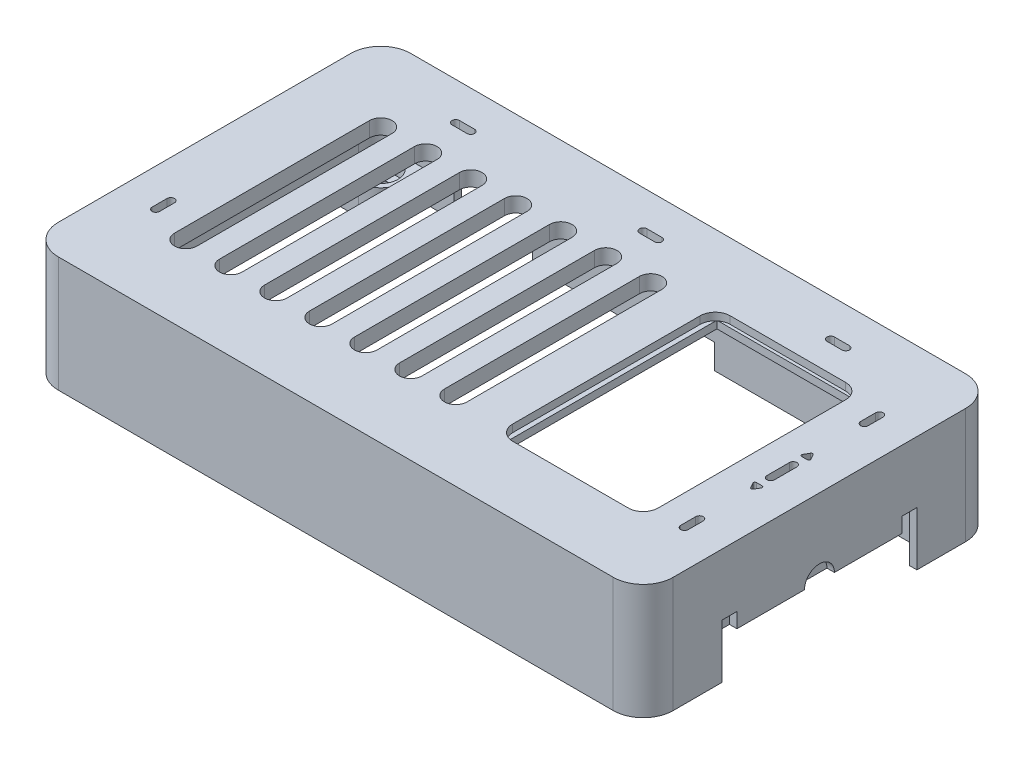
SolidWorks part; units mm, degrees
ref_plane "前视基准面" through (0, 0, 0) normal (0, 0, 1) x (1, 0, 0)
ref_plane "上视基准面" through (0, 0, 0) normal (0, 1, 0) x (1, 0, 0)
ref_plane "右视基准面" through (0, 0, 0) normal (1, 0, 0) x (0, 0, -1)
sketch "草图1" plane through (0, 0, 0) normal (0, 1, 0) x (1, 0, 0)
  line L0 (-1, -3) -> (-1, -42)
  line L1 (3, 0) -> (77, 0) construction
  line L2 (0, -3) -> (0, -42) construction
  line L3 (3, -45) -> (77, -45) construction
  line L4 (80, -3) -> (80, -42) construction
  line L5 (3, -46) -> (77, -46)
  line L6 (81, -3) -> (81, -42)
  line L7 (3, 1) -> (77, 1)
  arc A0 (3, -45) -> (0, -42) centre (3, -42) cw construction
  arc A1 (77, -45) -> (80, -42) centre (77, -42) ccw construction
  arc A2 (80, -3) -> (77, 0) centre (77, -3) ccw construction
  arc A3 (3, 0) -> (0, -3) centre (3, -3) ccw construction
  arc A4 (3, -46) -> (-1, -42) centre (3, -42) cw
  arc A5 (77, -46) -> (81, -42) centre (77, -42) ccw
  arc A6 (81, -3) -> (77, 1) centre (77, -3) ccw
  arc A7 (3, 1) -> (-1, -3) centre (3, -3) ccw
  point P5 (0, 0)
  point P14 (0, 0)
  dimension "D1" = 3
  dimension "D2" = 1
extrude "凸台-拉伸1" add sketch "草图1" against normal blind 2
sketch "草图2" plane through (0, 0, 0) normal (0, 1, 0) x (1, 0, 0)
  line L0 (0, -3) -> (0, -42) construction
  line L1 (3, -45) -> (77, -45) construction
  line L2 (80, -42) -> (80, -3) construction
  line L3 (77, 0) -> (3, 0) construction
  line L4 (-1, -3) -> (-1, -42)
  line L5 (77, 1) -> (3, 1)
  line L6 (81, -42) -> (81, -3)
  line L7 (3, -46) -> (77, -46)
  line L8 (-1, -3) -> (-1, -42) construction
  line L9 (77, 1) -> (3, 1) construction
  line L10 (81, -42) -> (81, -3) construction
  line L11 (3, -46) -> (77, -46) construction
  line L12 (39, -4) -> (41, -4) construction
  line L13 (0, 0) -> (80, 0) construction
  line L14 (0, 0) -> (0, -4) construction
  line L15 (0, -4) -> (80, -4) construction
  line L16 (80, 0) -> (80, -4) construction
  line L17 (39, -3.5) -> (41, -3.5)
  line L18 (39, -4.5) -> (41, -4.5)
  line L19 (0, -4) -> (15, -4) construction
  line L20 (14, -4) -> (16, -4) construction
  line L21 (14, -3.5) -> (16, -3.5)
  line L22 (14, -4.5) -> (16, -4.5)
  line L23 (80, -4) -> (65, -4) construction
  line L24 (64, -4) -> (66, -4) construction
  line L25 (64, -3.5) -> (66, -3.5)
  line L26 (64, -4.5) -> (66, -4.5)
  line L27 (76, -22.5) -> (76, -19.064) construction
  line L28 (80, 0) -> (76, 0) construction
  line L29 (80, 0) -> (80, -45) construction
  line L30 (80, -45) -> (76, -45) construction
  line L31 (76, 0) -> (76, -45) construction
  line L32 (76, -21) -> (76, -24) construction
  line L33 (76.5, -21) -> (76.5, -24)
  line L34 (75.5, -21) -> (75.5, -24)
  line L35 (76, -22.5) -> (76, -25.936) construction
  line L36 (75.8268, -18.514) -> (75.4371, -19.189)
  line L37 (75.6103, -19.489) -> (76.3897, -19.489)
  line L38 (76.5629, -19.189) -> (76.1732, -18.514)
  line L39 (76, -22.5) -> (76, -10.5) construction
  line L40 (76.1732, -26.486) -> (76.5629, -25.811)
  line L41 (76.3897, -25.511) -> (75.6103, -25.511)
  line L42 (75.4371, -25.811) -> (75.8268, -26.486)
  line L43 (76, -9.5) -> (76, -11.5) construction
  line L44 (76.5, -9.5) -> (76.5, -11.5)
  line L45 (75.5, -9.5) -> (75.5, -11.5)
  line L46 (76, -22.5) -> (76, -34.5) construction
  line L47 (76, -33.5) -> (76, -35.5) construction
  line L48 (76.5, -33.5) -> (76.5, -35.5)
  line L49 (75.5, -33.5) -> (75.5, -35.5)
  line L50 (4, 0) -> (4, -33) construction
  line L51 (0, 0) -> (4, 0) construction
  line L52 (0, 0) -> (0, -45) construction
  line L53 (0, -45) -> (4, -45) construction
  line L54 (4, 0) -> (4, -45) construction
  line L55 (4, -32) -> (4, -34) construction
  line L56 (4.5, -32) -> (4.5, -34)
  line L57 (3.5, -32) -> (3.5, -34)
  line L58 (70, -8) -> (54.5978, -8)
  line L59 (80, 0) -> (70, 0) construction
  line L60 (80, 0) -> (80, -10) construction
  line L61 (80, -10) -> (70, -10) construction
  line L62 (70, 0) -> (70, -10) construction
  line L63 (80, -45) -> (70, -45) construction
  line L64 (80, -45) -> (80, -35) construction
  line L65 (80, -35) -> (70, -35) construction
  line L66 (70, -45) -> (70, -35) construction
  line L67 (70, -10) -> (54.5978, -10) construction
  line L68 (70, -10) -> (70, -35) construction
  line L69 (70, -35) -> (54.5978, -35) construction
  line L70 (54.5978, -10) -> (54.5978, -35) construction
  line L71 (52.5978, -10) -> (52.5978, -35)
  line L72 (70, -37) -> (54.5978, -37)
  line L73 (72, -10) -> (72, -35)
  line L74 (72, -37) -> (52.5978, -37) construction
  line L75 (72, -8) -> (72, -37) construction
  line L76 (52.5978, -8) -> (52.5978, -37) construction
  line L77 (72, -8) -> (52.5978, -8) construction
  line L78 (54.5978, -8) -> (70, -8) construction
  line L79 (54.5978, -37) -> (70, -37) construction
  line L80 (8, -8) -> (9.5, -8) construction
  line L85 (0, 0) -> (8, 0) construction
  line L86 (0, 0) -> (0, -8) construction
  line L87 (0, -8) -> (8, -8) construction
  line L88 (8, -0.0281) -> (8, -8.0281) construction
  line L89 (9.5, -9.5) -> (9.5, -35.5) construction
  line L90 (8, -8) -> (9.5, -8) construction
  line L91 (8, -8) -> (8, -9.5) construction
  line L92 (8, -9.5) -> (9.5, -9.5) construction
  line L93 (9.5, -8) -> (9.5, -9.5) construction
  line L94 (8, -37) -> (9.5, -37) construction
  line L95 (8, -37) -> (8, -35.5) construction
  line L96 (8, -35.5) -> (9.5, -35.5) construction
  line L97 (9.5, -37) -> (9.5, -35.5) construction
  line L98 (11, -9.5) -> (11, -35.5)
  line L99 (8, -9.5) -> (8, -35.5)
  line L100 (15.5, -9.5) -> (15.5, -35.5) construction
  line L101 (17, -9.5) -> (17, -35.5)
  line L102 (14, -9.5) -> (14, -35.5)
  line L103 (21.5, -9.5) -> (21.5, -35.5) construction
  line L104 (23, -9.5) -> (23, -35.5)
  line L105 (20, -9.5) -> (20, -35.5)
  line L106 (27.5, -9.5) -> (27.5, -35.5) construction
  line L107 (29, -9.5) -> (29, -35.5)
  line L108 (26, -9.5) -> (26, -35.5)
  line L109 (33.5, -9.5) -> (33.5, -35.5) construction
  line L110 (35, -9.5) -> (35, -35.5)
  line L111 (32, -9.5) -> (32, -35.5)
  line L112 (39.5, -9.5) -> (39.5, -35.5) construction
  line L113 (41, -9.5) -> (41, -35.5)
  line L114 (38, -9.5) -> (38, -35.5)
  line L115 (45.5, -9.5) -> (45.5, -35.5) construction
  line L116 (47, -9.5) -> (47, -35.5)
  line L117 (44, -9.5) -> (44, -35.5)
  arc A0 (0, -42) -> (3, -45) centre (3, -42) ccw construction
  arc A1 (77, -45) -> (80, -42) centre (77, -42) ccw construction
  arc A2 (80, -3) -> (77, 0) centre (77, -3) ccw construction
  arc A3 (3, 0) -> (0, -3) centre (3, -3) ccw construction
  arc A4 (3, 1) -> (-1, -3) centre (3, -3) ccw
  arc A5 (81, -3) -> (77, 1) centre (77, -3) ccw
  arc A6 (77, -46) -> (81, -42) centre (77, -42) ccw
  arc A7 (-1, -42) -> (3, -46) centre (3, -42) ccw
  arc A8 (3, 1) -> (-1, -3) centre (3, -3) ccw construction
  arc A9 (81, -3) -> (77, 1) centre (77, -3) ccw construction
  arc A10 (77, -46) -> (81, -42) centre (77, -42) ccw construction
  arc A11 (-1, -42) -> (3, -46) centre (3, -42) ccw construction
  arc A12 (39, -3.5) -> (39, -4.5) centre (39, -4) ccw
  arc A13 (41, -4.5) -> (41, -3.5) centre (41, -4) ccw
  arc A14 (14, -3.5) -> (14, -4.5) centre (14, -4) ccw
  arc A15 (16, -4.5) -> (16, -3.5) centre (16, -4) ccw
  arc A16 (64, -3.5) -> (64, -4.5) centre (64, -4) ccw
  arc A17 (66, -4.5) -> (66, -3.5) centre (66, -4) ccw
  arc A19 (76.5, -21) -> (75.5, -21) centre (76, -21) ccw
  arc A20 (75.5, -24) -> (76.5, -24) centre (76, -24) ccw
  circle A21 centre (76, -19.064) radius 0.85 construction
  arc A22 (76.5629, -19.189) -> (76.3897, -19.489) centre (76.3897, -19.289) cw
  arc A23 (76.1732, -18.514) -> (75.8268, -18.514) centre (76, -18.614) ccw
  arc A24 (75.4371, -19.189) -> (75.6103, -19.489) centre (75.6103, -19.289) ccw
  circle A25 centre (76, -25.936) radius 0.85 construction
  arc A26 (76.1732, -26.486) -> (75.8268, -26.486) centre (76, -26.386) cw
  arc A27 (76.3897, -25.511) -> (76.5629, -25.811) centre (76.3897, -25.711) cw
  arc A28 (75.6103, -25.511) -> (75.4371, -25.811) centre (75.6103, -25.711) ccw
  arc A29 (76.5, -9.5) -> (75.5, -9.5) centre (76, -9.5) ccw
  arc A30 (75.5, -11.5) -> (76.5, -11.5) centre (76, -11.5) ccw
  arc A31 (76.5, -33.5) -> (75.5, -33.5) centre (76, -33.5) ccw
  arc A32 (75.5, -35.5) -> (76.5, -35.5) centre (76, -35.5) ccw
  arc A33 (4.5, -32) -> (3.5, -32) centre (4, -32) ccw
  arc A34 (3.5, -34) -> (4.5, -34) centre (4, -34) ccw
  arc A35 (70, -37) -> (72, -35) centre (70, -35) ccw
  arc A36 (54.5978, -37) -> (52.5978, -35) centre (54.5978, -35) cw
  arc A37 (72, -10) -> (70, -8) centre (70, -10) ccw
  arc A38 (54.5978, -8) -> (52.5978, -10) centre (54.5978, -10) ccw
  arc A39 (11, -9.5) -> (8, -9.5) centre (9.5, -9.5) ccw
  arc A40 (8, -35.5) -> (11, -35.5) centre (9.5, -35.5) ccw
  arc A41 (17, -9.5) -> (14, -9.5) centre (15.5, -9.5) ccw
  arc A42 (14, -35.5) -> (17, -35.5) centre (15.5, -35.5) ccw
  arc A43 (23, -9.5) -> (20, -9.5) centre (21.5, -9.5) ccw
  arc A44 (20, -35.5) -> (23, -35.5) centre (21.5, -35.5) ccw
  arc A45 (29, -9.5) -> (26, -9.5) centre (27.5, -9.5) ccw
  arc A46 (26, -35.5) -> (29, -35.5) centre (27.5, -35.5) ccw
  arc A47 (35, -9.5) -> (32, -9.5) centre (33.5, -9.5) ccw
  arc A48 (32, -35.5) -> (35, -35.5) centre (33.5, -35.5) ccw
  arc A49 (41, -9.5) -> (38, -9.5) centre (39.5, -9.5) ccw
  arc A50 (38, -35.5) -> (41, -35.5) centre (39.5, -35.5) ccw
  arc A51 (47, -9.5) -> (44, -9.5) centre (45.5, -9.5) ccw
  arc A52 (44, -35.5) -> (47, -35.5) centre (45.5, -35.5) ccw
  point P31 (40, -4)
  point P38 (15, -4)
  point P46 (65, -4)
  point P59 (76, -22.5)
  point P70 (76.7361, -19.489)
  point P86 (75.2639, -25.511)
  point P89 (76, -10.5)
  point P97 (76, -34.5)
  point P109 (4, -33)
  point P154 (9.5, -22.5)
  point P159 (0, 0)
  point P162 (15.5, -22.5)
  point P169 (21.5, -22.5)
  point P176 (27.5, -22.5)
  point P183 (33.5, -22.5)
  point P190 (39.5, -22.5)
  point P197 (45.5, -22.5)
  dimension "D3" = 0.2
  dimension "D4" = 0.2
  dimension "D5" = 2
  dimension "D6" = 2
  dimension "D7" = 7
  dimension "D1" = 0
  dimension "D2" = 1
extrude "切除-拉伸1" cut sketch "草图2" against normal blind 1
sketch "草图3" plane through (0, -2, 0) normal (0, -1, 0) x (1, 0, 0)
  line L0 (76, 11.5) -> (76, 9.5) construction
  line L1 (76, 24) -> (76, 21) construction
  line L2 (14, 3.5) -> (16, 3.5)
  line L3 (16, 4.5) -> (14, 4.5)
  line L4 (14, 3.5) -> (16, 3.5) construction
  line L5 (16, 4.5) -> (14, 4.5) construction
  line L6 (39, 3.5) -> (41, 3.5)
  line L7 (41, 4.5) -> (39, 4.5)
  line L8 (39, 3.5) -> (41, 3.5) construction
  line L9 (41, 4.5) -> (39, 4.5) construction
  line L10 (76.5, 21) -> (76.5, 24)
  line L11 (75.5, 24) -> (75.5, 21)
  line L12 (76.5, 21) -> (76.5, 24) construction
  line L13 (75.5, 24) -> (75.5, 21) construction
  line L14 (64, 3.5) -> (66, 3.5)
  line L15 (66, 4.5) -> (64, 4.5)
  line L16 (64, 3.5) -> (66, 3.5) construction
  line L17 (66, 4.5) -> (64, 4.5) construction
  line L18 (76.5, 9.5) -> (76.5, 11.5)
  line L19 (75.4371, 19.189) -> (75.8268, 18.514)
  line L20 (76.3897, 19.489) -> (75.6103, 19.489)
  line L21 (76.1732, 18.514) -> (76.5629, 19.189)
  line L22 (75.4371, 19.189) -> (75.8268, 18.514) construction
  line L23 (76.3897, 19.489) -> (75.6103, 19.489) construction
  line L24 (76.1732, 18.514) -> (76.5629, 19.189) construction
  line L25 (75.5, 11.5) -> (75.5, 9.5)
  line L26 (76.5, 9.5) -> (76.5, 11.5) construction
  line L27 (75.5, 11.5) -> (75.5, 9.5) construction
  line L28 (76.5, 33.5) -> (76.5, 35.5)
  line L29 (76.5629, 25.811) -> (76.1732, 26.486)
  line L30 (75.8268, 26.486) -> (75.4371, 25.811)
  line L31 (75.6103, 25.511) -> (76.3897, 25.511)
  line L32 (76.5629, 25.811) -> (76.1732, 26.486) construction
  line L33 (75.8268, 26.486) -> (75.4371, 25.811) construction
  line L34 (75.6103, 25.511) -> (76.3897, 25.511) construction
  line L35 (75.5, 35.5) -> (75.5, 33.5)
  line L36 (76.5, 33.5) -> (76.5, 35.5) construction
  line L37 (75.5, 35.5) -> (75.5, 33.5) construction
  line L38 (3.5, 34) -> (3.5, 32)
  line L39 (4.5, 32) -> (4.5, 34)
  line L40 (3.5, 34) -> (3.5, 32) construction
  line L41 (4.5, 32) -> (4.5, 34) construction
  line L42 (11, 9.5) -> (11, 35.5)
  line L43 (8, 35.5) -> (8, 9.5)
  line L44 (54.5978, 8) -> (70, 8)
  line L45 (52.5978, 35) -> (52.5978, 10)
  line L46 (70, 37) -> (54.5978, 37)
  line L47 (72, 10) -> (72, 35)
  line L48 (54.5978, 8) -> (70, 8) construction
  line L49 (52.5978, 35) -> (52.5978, 10) construction
  line L50 (70, 37) -> (54.5978, 37) construction
  line L51 (72, 10) -> (72, 35) construction
  line L52 (11, 9.5) -> (11, 35.5) construction
  line L53 (8, 35.5) -> (8, 9.5) construction
  line L54 (23, 9.5) -> (23, 35.5)
  line L55 (20, 35.5) -> (20, 9.5)
  line L56 (23, 9.5) -> (23, 35.5) construction
  line L57 (20, 35.5) -> (20, 9.5) construction
  line L58 (17, 9.5) -> (17, 35.5)
  line L59 (14, 35.5) -> (14, 9.5)
  line L60 (17, 9.5) -> (17, 35.5) construction
  line L61 (14, 35.5) -> (14, 9.5) construction
  line L62 (35, 9.5) -> (35, 35.5)
  line L63 (32, 35.5) -> (32, 9.5)
  line L64 (35, 9.5) -> (35, 35.5) construction
  line L65 (32, 35.5) -> (32, 9.5) construction
  line L66 (29, 9.5) -> (29, 35.5)
  line L67 (26, 35.5) -> (26, 9.5)
  line L68 (29, 9.5) -> (29, 35.5) construction
  line L69 (26, 35.5) -> (26, 9.5) construction
  line L70 (47, 9.5) -> (47, 35.5)
  line L71 (44, 35.5) -> (44, 9.5)
  line L72 (47, 9.5) -> (47, 35.5) construction
  line L73 (44, 35.5) -> (44, 9.5) construction
  line L74 (38, 35.5) -> (38, 9.5)
  line L75 (41, 9.5) -> (41, 35.5)
  line L76 (38, 35.5) -> (38, 9.5) construction
  line L77 (41, 9.5) -> (41, 35.5) construction
  line L78 (74.75, 20.314) -> (77.25, 20.314)
  line L79 (74.75, 21.25) -> (77.25, 21.25)
  line L80 (74.75, 21.25) -> (74.75, 23.75)
  line L81 (74.75, 23.75) -> (77.25, 23.75)
  line L82 (77.25, 21.25) -> (77.25, 23.75)
  line L83 (74.75, 21.25) -> (77.25, 23.75) construction
  line L84 (74.75, 23.75) -> (77.25, 21.25) construction
  line L85 (74.75, 24.686) -> (77.25, 24.686)
  line L86 (74.75, 24.686) -> (74.75, 27.186)
  line L87 (74.75, 27.186) -> (77.25, 27.186)
  line L88 (77.25, 24.686) -> (77.25, 27.186)
  line L89 (74.75, 24.686) -> (77.25, 27.186) construction
  line L90 (74.75, 27.186) -> (77.25, 24.686) construction
  line L91 (74.75, 20.314) -> (74.75, 17.814)
  line L92 (74.75, 17.814) -> (77.25, 17.814)
  line L93 (77.25, 20.314) -> (77.25, 17.814)
  line L94 (74.75, 20.314) -> (77.25, 17.814) construction
  line L95 (74.75, 17.814) -> (77.25, 20.314) construction
  line L96 (76, 35.5) -> (76, 33.5) construction
  line L97 (74.75, 11.75) -> (77.25, 11.75)
  line L98 (74.75, 11.75) -> (74.75, 9.25)
  line L99 (74.75, 9.25) -> (77.25, 9.25)
  line L100 (77.25, 11.75) -> (77.25, 9.25)
  line L101 (74.75, 11.75) -> (77.25, 9.25) construction
  line L102 (74.75, 9.25) -> (77.25, 11.75) construction
  line L103 (64, 4) -> (66, 4) construction
  line L104 (74.75, 35.75) -> (77.25, 35.75)
  line L105 (74.75, 35.75) -> (74.75, 33.25)
  line L106 (74.75, 33.25) -> (77.25, 33.25)
  line L107 (77.25, 35.75) -> (77.25, 33.25)
  line L108 (74.75, 35.75) -> (77.25, 33.25) construction
  line L109 (74.75, 33.25) -> (77.25, 35.75) construction
  line L110 (39, 4) -> (41, 4) construction
  line L111 (14, 4) -> (16, 4) construction
  line L112 (4, 34) -> (4, 32) construction
  line L115 (63.75, 5.25) -> (63.75, 2.75)
  line L116 (63.75, 2.75) -> (66.25, 2.75)
  line L117 (66.25, 5.25) -> (66.25, 2.75)
  line L118 (63.75, 5.25) -> (66.25, 2.75) construction
  line L119 (63.75, 2.75) -> (66.25, 5.25) construction
  line L121 (38.75, 5.25) -> (38.75, 2.75)
  line L122 (38.75, 2.75) -> (41.25, 2.75)
  line L123 (41.25, 5.25) -> (41.25, 2.75)
  line L124 (38.75, 5.25) -> (41.25, 2.75) construction
  line L125 (38.75, 2.75) -> (41.25, 5.25) construction
  line L127 (13.75, 5.25) -> (13.75, 2.75)
  line L128 (13.75, 2.75) -> (16.25, 2.75)
  line L129 (16.25, 5.25) -> (16.25, 2.75)
  line L130 (13.75, 5.25) -> (16.25, 2.75) construction
  line L131 (13.75, 2.75) -> (16.25, 5.25) construction
  line L132 (2.75, 34.25) -> (5.25, 34.25)
  line L133 (2.75, 34.25) -> (2.75, 31.75)
  line L134 (2.75, 31.75) -> (5.25, 31.75)
  line L135 (5.25, 34.25) -> (5.25, 31.75)
  line L136 (2.75, 34.25) -> (5.25, 31.75) construction
  line L137 (2.75, 31.75) -> (5.25, 34.25) construction
  line L138 (70, 10) -> (71.37, 10) construction
  line L139 (70, 10) -> (70, 8.4) construction
  line L140 (70, 8.4) -> (71.37, 8.4) construction
  line L141 (71.37, 10) -> (71.37, 8.4) construction
  line L142 (54.5978, 10) -> (53.2278, 10) construction
  line L143 (54.5978, 10) -> (54.5978, 8.4) construction
  line L144 (54.5978, 8.4) -> (53.2278, 8.4) construction
  line L145 (3, 0) -> (77, 0)
  line L146 (80, 3) -> (80, 42)
  line L147 (77, 45) -> (3, 45)
  line L148 (0, 42) -> (0, 3)
  line L149 (3, 0) -> (77, 0) construction
  line L150 (80, 3) -> (80, 42) construction
  line L151 (77, 45) -> (3, 45) construction
  line L152 (0, 42) -> (0, 3) construction
  line L153 (53.2278, 10) -> (53.2278, 8.4) construction
  line L154 (53.2278, 8.4) -> (71.37, 8.4)
  line L155 (53.2278, 8.4) -> (53.2278, 40.4)
  line L156 (53.2278, 40.4) -> (71.37, 40.4)
  line L157 (71.37, 8.4) -> (71.37, 40.4)
  line L159 (13.75, 5.25) -> (13.75, 6.25)
  line L160 (13.75, 6.25) -> (16.25, 6.25)
  line L161 (16.25, 5.25) -> (16.25, 6.25)
  line L163 (38.75, 5.25) -> (38.75, 6.25)
  line L164 (38.75, 6.25) -> (41.25, 6.25)
  line L165 (41.25, 5.25) -> (41.25, 6.25)
  line L167 (63.75, 5.25) -> (63.75, 6.25)
  line L168 (63.75, 6.25) -> (66.25, 6.25)
  line L169 (66.25, 5.25) -> (66.25, 6.25)
  circle A0 centre (76, 25.936) radius 0.45 construction
  circle A1 centre (76, 19.064) radius 0.45 construction
  arc A2 (16, 3.5) -> (16, 4.5) centre (16, 4) ccw
  arc A3 (14, 4.5) -> (14, 3.5) centre (14, 4) ccw
  arc A4 (16, 3.5) -> (16, 4.5) centre (16, 4) ccw construction
  arc A5 (14, 4.5) -> (14, 3.5) centre (14, 4) ccw construction
  arc A6 (41, 3.5) -> (41, 4.5) centre (41, 4) ccw
  arc A7 (39, 4.5) -> (39, 3.5) centre (39, 4) ccw
  arc A8 (41, 3.5) -> (41, 4.5) centre (41, 4) ccw construction
  arc A9 (39, 4.5) -> (39, 3.5) centre (39, 4) ccw construction
  arc A10 (76.5, 24) -> (75.5, 24) centre (76, 24) ccw
  arc A11 (75.5, 21) -> (76.5, 21) centre (76, 21) ccw
  arc A12 (76.5, 24) -> (75.5, 24) centre (76, 24) ccw construction
  arc A13 (75.5, 21) -> (76.5, 21) centre (76, 21) ccw construction
  arc A14 (66, 3.5) -> (66, 4.5) centre (66, 4) ccw
  arc A15 (64, 4.5) -> (64, 3.5) centre (64, 4) ccw
  arc A16 (66, 3.5) -> (66, 4.5) centre (66, 4) ccw construction
  arc A17 (64, 4.5) -> (64, 3.5) centre (64, 4) ccw construction
  arc A18 (76.5, 11.5) -> (75.5, 11.5) centre (76, 11.5) ccw
  arc A19 (75.6103, 19.489) -> (75.4371, 19.189) centre (75.6103, 19.289) ccw
  arc A20 (76.5629, 19.189) -> (76.3897, 19.489) centre (76.3897, 19.289) ccw
  arc A21 (75.8268, 18.514) -> (76.1732, 18.514) centre (76, 18.614) ccw
  arc A22 (75.6103, 19.489) -> (75.4371, 19.189) centre (75.6103, 19.289) ccw construction
  arc A23 (76.5629, 19.189) -> (76.3897, 19.489) centre (76.3897, 19.289) ccw construction
  arc A24 (75.8268, 18.514) -> (76.1732, 18.514) centre (76, 18.614) ccw construction
  arc A25 (75.5, 9.5) -> (76.5, 9.5) centre (76, 9.5) ccw
  arc A26 (76.5, 11.5) -> (75.5, 11.5) centre (76, 11.5) ccw construction
  arc A27 (75.5, 9.5) -> (76.5, 9.5) centre (76, 9.5) ccw construction
  arc A28 (76.5, 35.5) -> (75.5, 35.5) centre (76, 35.5) ccw
  arc A29 (76.1732, 26.486) -> (75.8268, 26.486) centre (76, 26.386) ccw
  arc A30 (75.4371, 25.811) -> (75.6103, 25.511) centre (75.6103, 25.711) ccw
  arc A31 (76.3897, 25.511) -> (76.5629, 25.811) centre (76.3897, 25.711) ccw
  arc A32 (76.1732, 26.486) -> (75.8268, 26.486) centre (76, 26.386) ccw construction
  arc A33 (75.4371, 25.811) -> (75.6103, 25.511) centre (75.6103, 25.711) ccw construction
  arc A34 (76.3897, 25.511) -> (76.5629, 25.811) centre (76.3897, 25.711) ccw construction
  arc A35 (75.5, 33.5) -> (76.5, 33.5) centre (76, 33.5) ccw
  arc A36 (76.5, 35.5) -> (75.5, 35.5) centre (76, 35.5) ccw construction
  arc A37 (75.5, 33.5) -> (76.5, 33.5) centre (76, 33.5) ccw construction
  arc A38 (4.5, 34) -> (3.5, 34) centre (4, 34) ccw
  arc A39 (3.5, 32) -> (4.5, 32) centre (4, 32) ccw
  arc A40 (4.5, 34) -> (3.5, 34) centre (4, 34) ccw construction
  arc A41 (3.5, 32) -> (4.5, 32) centre (4, 32) ccw construction
  arc A42 (11, 35.5) -> (8, 35.5) centre (9.5, 35.5) ccw
  arc A43 (8, 9.5) -> (11, 9.5) centre (9.5, 9.5) ccw
  arc A44 (52.5978, 10) -> (54.5978, 8) centre (54.5978, 10) ccw
  arc A45 (54.5978, 37) -> (52.5978, 35) centre (54.5978, 35) ccw
  arc A46 (72, 35) -> (70, 37) centre (70, 35) ccw
  arc A47 (70, 8) -> (72, 10) centre (70, 10) ccw
  arc A48 (52.5978, 10) -> (54.5978, 8) centre (54.5978, 10) ccw construction
  arc A49 (54.5978, 37) -> (52.5978, 35) centre (54.5978, 35) ccw construction
  arc A50 (72, 35) -> (70, 37) centre (70, 35) ccw construction
  arc A51 (70, 8) -> (72, 10) centre (70, 10) ccw construction
  arc A52 (11, 35.5) -> (8, 35.5) centre (9.5, 35.5) ccw construction
  arc A53 (8, 9.5) -> (11, 9.5) centre (9.5, 9.5) ccw construction
  arc A54 (23, 35.5) -> (20, 35.5) centre (21.5, 35.5) ccw
  arc A55 (20, 9.5) -> (23, 9.5) centre (21.5, 9.5) ccw
  arc A56 (23, 35.5) -> (20, 35.5) centre (21.5, 35.5) ccw construction
  arc A57 (20, 9.5) -> (23, 9.5) centre (21.5, 9.5) ccw construction
  arc A58 (17, 35.5) -> (14, 35.5) centre (15.5, 35.5) ccw
  arc A59 (14, 9.5) -> (17, 9.5) centre (15.5, 9.5) ccw
  arc A60 (17, 35.5) -> (14, 35.5) centre (15.5, 35.5) ccw construction
  arc A61 (14, 9.5) -> (17, 9.5) centre (15.5, 9.5) ccw construction
  arc A62 (35, 35.5) -> (32, 35.5) centre (33.5, 35.5) ccw
  arc A63 (32, 9.5) -> (35, 9.5) centre (33.5, 9.5) ccw
  arc A64 (35, 35.5) -> (32, 35.5) centre (33.5, 35.5) ccw construction
  arc A65 (32, 9.5) -> (35, 9.5) centre (33.5, 9.5) ccw construction
  arc A66 (29, 35.5) -> (26, 35.5) centre (27.5, 35.5) ccw
  arc A67 (26, 9.5) -> (29, 9.5) centre (27.5, 9.5) ccw
  arc A68 (29, 35.5) -> (26, 35.5) centre (27.5, 35.5) ccw construction
  arc A69 (26, 9.5) -> (29, 9.5) centre (27.5, 9.5) ccw construction
  arc A70 (47, 35.5) -> (44, 35.5) centre (45.5, 35.5) ccw
  arc A71 (44, 9.5) -> (47, 9.5) centre (45.5, 9.5) ccw
  arc A72 (47, 35.5) -> (44, 35.5) centre (45.5, 35.5) ccw construction
  arc A73 (44, 9.5) -> (47, 9.5) centre (45.5, 9.5) ccw construction
  arc A74 (41, 35.5) -> (38, 35.5) centre (39.5, 35.5) ccw
  arc A75 (38, 9.5) -> (41, 9.5) centre (39.5, 9.5) ccw
  arc A76 (41, 35.5) -> (38, 35.5) centre (39.5, 35.5) ccw construction
  arc A77 (38, 9.5) -> (41, 9.5) centre (39.5, 9.5) ccw construction
  arc A86 (0, 3) -> (3, 0) centre (3, 3) ccw
  arc A87 (77, 0) -> (80, 3) centre (77, 3) ccw
  arc A88 (80, 42) -> (77, 45) centre (77, 42) ccw
  arc A89 (3, 45) -> (0, 42) centre (3, 42) ccw
  arc A90 (0, 3) -> (3, 0) centre (3, 3) ccw construction
  arc A91 (77, 0) -> (80, 3) centre (77, 3) ccw construction
  arc A92 (80, 42) -> (77, 45) centre (77, 42) ccw construction
  arc A93 (3, 45) -> (0, 42) centre (3, 42) ccw construction
  point P104 (76, 22.5)
  point P131 (76, 10.5)
  point P136 (76, 34.5)
  point P141 (65, 4)
  point P146 (40, 4)
  point P151 (15, 4)
  point P156 (4, 33)
  dimension "D18" = 1
  dimension "D1" = 0
  dimension "D2" = 0
  dimension "D3" = 0
  dimension "D4" = 0
  dimension "D5" = 0
  dimension "D6" = 0
  dimension "D7" = 0
  dimension "D8" = 0
  dimension "D9" = 0
  dimension "D10" = 0
  dimension "D11" = 0
  dimension "D12" = 0
  dimension "D13" = 0
  dimension "D14" = 0
  dimension "D15" = 0
  dimension "D16" = 0
  dimension "D17" = 0
extrude "切除-拉伸2" cut sketch "草图3" against normal blind 1
sketch "草图4" plane through (0, 0, 0) normal (0, 1, 0) x (1, 0, 0)
  line L42 (11, -35.5) -> (11, -9.5)
  line L43 (8, -9.5) -> (8, -35.5)
  line L52 (11, -35.5) -> (11, -9.5)
  line L53 (8, -9.5) -> (8, -35.5)
  line L54 (23, -35.5) -> (23, -9.5)
  line L55 (20, -9.5) -> (20, -35.5)
  line L56 (23, -35.5) -> (23, -9.5)
  line L57 (20, -9.5) -> (20, -35.5)
  line L58 (17, -35.5) -> (17, -9.5)
  line L59 (14, -9.5) -> (14, -35.5)
  line L60 (17, -35.5) -> (17, -9.5)
  line L61 (14, -9.5) -> (14, -35.5)
  line L62 (35, -35.5) -> (35, -9.5)
  line L63 (32, -9.5) -> (32, -35.5)
  line L64 (35, -35.5) -> (35, -9.5)
  line L65 (32, -9.5) -> (32, -35.5)
  line L66 (29, -35.5) -> (29, -9.5)
  line L67 (26, -9.5) -> (26, -35.5)
  line L68 (29, -35.5) -> (29, -9.5)
  line L69 (26, -9.5) -> (26, -35.5)
  line L70 (47, -35.5) -> (47, -9.5)
  line L71 (44, -9.5) -> (44, -35.5)
  line L72 (47, -35.5) -> (47, -9.5)
  line L73 (44, -9.5) -> (44, -35.5)
  line L74 (38, -9.5) -> (38, -35.5)
  line L75 (41, -35.5) -> (41, -9.5)
  line L76 (38, -9.5) -> (38, -35.5)
  line L77 (41, -35.5) -> (41, -9.5)
  arc A42 (8, -35.5) -> (11, -35.5) centre (9.5, -35.5) ccw
  arc A43 (11, -9.5) -> (8, -9.5) centre (9.5, -9.5) ccw
  arc A52 (8, -35.5) -> (11, -35.5) centre (9.5, -35.5) ccw
  arc A53 (11, -9.5) -> (8, -9.5) centre (9.5, -9.5) ccw
  arc A54 (20, -35.5) -> (23, -35.5) centre (21.5, -35.5) ccw
  arc A55 (23, -9.5) -> (20, -9.5) centre (21.5, -9.5) ccw
  arc A56 (20, -35.5) -> (23, -35.5) centre (21.5, -35.5) ccw
  arc A57 (23, -9.5) -> (20, -9.5) centre (21.5, -9.5) ccw
  arc A58 (14, -35.5) -> (17, -35.5) centre (15.5, -35.5) ccw
  arc A59 (17, -9.5) -> (14, -9.5) centre (15.5, -9.5) ccw
  arc A60 (14, -35.5) -> (17, -35.5) centre (15.5, -35.5) ccw
  arc A61 (17, -9.5) -> (14, -9.5) centre (15.5, -9.5) ccw
  arc A62 (32, -35.5) -> (35, -35.5) centre (33.5, -35.5) ccw
  arc A63 (35, -9.5) -> (32, -9.5) centre (33.5, -9.5) ccw
  arc A64 (32, -35.5) -> (35, -35.5) centre (33.5, -35.5) ccw
  arc A65 (35, -9.5) -> (32, -9.5) centre (33.5, -9.5) ccw
  arc A66 (26, -35.5) -> (29, -35.5) centre (27.5, -35.5) ccw
  arc A67 (29, -9.5) -> (26, -9.5) centre (27.5, -9.5) ccw
  arc A68 (26, -35.5) -> (29, -35.5) centre (27.5, -35.5) ccw
  arc A69 (29, -9.5) -> (26, -9.5) centre (27.5, -9.5) ccw
  arc A70 (44, -35.5) -> (47, -35.5) centre (45.5, -35.5) ccw
  arc A71 (47, -9.5) -> (44, -9.5) centre (45.5, -9.5) ccw
  arc A72 (44, -35.5) -> (47, -35.5) centre (45.5, -35.5) ccw
  arc A73 (47, -9.5) -> (44, -9.5) centre (45.5, -9.5) ccw
  arc A74 (38, -35.5) -> (41, -35.5) centre (39.5, -35.5) ccw
  arc A75 (41, -9.5) -> (38, -9.5) centre (39.5, -9.5) ccw
  arc A76 (38, -35.5) -> (41, -35.5) centre (39.5, -35.5) ccw
  arc A77 (41, -9.5) -> (38, -9.5) centre (39.5, -9.5) ccw
  dimension "D11" = 0
  dimension "D12" = 0
  dimension "D13" = 0
  dimension "D14" = 0
  dimension "D15" = 0
  dimension "D16" = 0
  dimension "D17" = 0
extrude "切除-拉伸3" cut sketch "草图4" against normal through all
sketch "草图5" plane through (0, -2, 0) normal (0, -1, 0) x (1, 0, 0)
  line L4 (3, -1) -> (77, -1)
  line L5 (81, 3) -> (81, 42)
  line L6 (77, 46) -> (3, 46)
  line L7 (-1, 42) -> (-1, 3)
  line L8 (3, 0) -> (77, 0)
  line L9 (80, 3) -> (80, 42)
  line L10 (77, 45) -> (3, 45)
  line L11 (0, 42) -> (0, 3)
  line L12 (3, 0) -> (77, 0)
  line L13 (80, 3) -> (80, 42)
  line L14 (77, 45) -> (3, 45)
  line L15 (0, 42) -> (0, 3)
  arc A4 (-1, 3) -> (3, -1) centre (3, 3) ccw
  arc A5 (77, -1) -> (81, 3) centre (77, 3) ccw
  arc A6 (81, 42) -> (77, 46) centre (77, 42) ccw
  arc A7 (3, 46) -> (-1, 42) centre (3, 42) ccw
  arc A8 (0, 3) -> (3, 0) centre (3, 3) ccw
  arc A9 (77, 0) -> (80, 3) centre (77, 3) ccw
  arc A10 (80, 42) -> (77, 45) centre (77, 42) ccw
  arc A11 (3, 45) -> (0, 42) centre (3, 42) ccw
  arc A12 (0, 3) -> (3, 0) centre (3, 3) ccw
  arc A13 (77, 0) -> (80, 3) centre (77, 3) ccw
  arc A14 (80, 42) -> (77, 45) centre (77, 42) ccw
  arc A15 (3, 45) -> (0, 42) centre (3, 42) ccw
  dimension "D1" = 1
  dimension "D2" = 1
extrude "凸台-拉伸2" add sketch "草图5" along normal blind 13.4
sketch "草图6" plane through (0, -15.4, 0) normal (0, -1, 0) x (1, 0, 0)
  line L0 (0, 0) -> (0, 33) construction
  line L1 (0, 42) -> (0, 3) construction
  line L2 (0, 33) -> (-0.5, 33) construction
  line L3 (0, 0) -> (15, 0) construction
  line L4 (-1, 38.25) -> (0, 38.25)
  line L5 (-1, 38.25) -> (-1, 27.75)
  line L6 (-1, 27.75) -> (0, 27.75)
  line L7 (0, 38.25) -> (0, 27.75)
  line L8 (-1, 38.25) -> (0, 27.75) construction
  line L9 (-1, 27.75) -> (0, 38.25) construction
  line L10 (3, 0) -> (77, 0) construction
  line L11 (15, 0) -> (15, -0.5) construction
  line L12 (3, -1) -> (77, -1) construction
  line L13 (9.75, 0) -> (20.25, 0)
  line L14 (9.75, 0) -> (9.75, -1)
  line L15 (9.75, -1) -> (20.25, -1)
  line L16 (20.25, 0) -> (20.25, -1)
  line L17 (9.75, 0) -> (20.25, -1) construction
  line L18 (9.75, -1) -> (20.25, 0) construction
extrude "切除-拉伸4" cut sketch "草图6" against normal blind 10.5
sketch "草图7" plane through (0, -15.4, 0) normal (0, -1, 0) x (1, 0, 0)
  line L0 (40, 0) -> (40, -0.5) construction
  line L1 (3, 0) -> (77, 0) construction
  line L2 (20.25, -1) -> (77, -1) construction
  line L3 (35.5, 0) -> (44.5, 0)
  line L4 (35.5, 0) -> (35.5, -1)
  line L5 (35.5, -1) -> (44.5, -1)
  line L6 (44.5, 0) -> (44.5, -1)
  line L7 (35.5, 0) -> (44.5, -1) construction
  line L8 (35.5, -1) -> (44.5, 0) construction
  line L10 (80, 3) -> (80, 42) construction
  line L11 (44.5, 0) -> (77, 0) construction
  line L12 (80, 0) -> (65, 0) construction
  line L13 (65, 0) -> (65, -0.5) construction
  line L15 (60.5, 0) -> (69.5, 0)
  line L16 (60.5, 0) -> (60.5, -1)
  line L17 (60.5, -1) -> (69.5, -1)
  line L18 (69.5, 0) -> (69.5, -1)
  line L19 (60.5, 0) -> (69.5, -1) construction
  line L20 (60.5, -1) -> (69.5, 0) construction
extrude "切除-拉伸5" cut sketch "草图7" against normal blind 3.3
sketch "草图8" plane through (0, -15.4, 0) normal (0, -1, 0) x (1, 0, 0)
  line L0 (81, 22.5) -> (80.5, 22.5) construction
  line L5 (81, 3) -> (81, 42) construction
  line L7 (80, 9.5) -> (81, 9.5)
  line L8 (80, 9.5) -> (80, 35.5)
  line L9 (80, 35.5) -> (81, 35.5)
  line L10 (81, 9.5) -> (81, 35.5)
  line L11 (80, 9.5) -> (81, 35.5) construction
  line L12 (80, 35.5) -> (81, 9.5) construction
extrude "切除-拉伸6" cut sketch "草图8" against normal blind 5.2
sketch "草图9" plane through (81, 0, 0) normal (1, 0, 0) x (0, 0, -1)
  line L0 (-9.5, -10.2) -> (-35.5, -10.2) construction
  line L1 (-22.5, -10.2) -> (-10.5, -10.2) construction
  line L2 (-22.5, -10.2) -> (-34.5, -10.2) construction
  line L3 (-35.5, -10.2) -> (-35.5, -15.4) construction
  line L4 (-33.5, -8.2) -> (-35.5, -8.2)
  line L5 (-33.5, -8.2) -> (-33.5, -12.2)
  line L6 (-33.5, -12.2) -> (-35.5, -12.2)
  line L7 (-35.5, -8.2) -> (-35.5, -12.2)
  line L8 (-33.5, -8.2) -> (-35.5, -12.2) construction
  line L9 (-33.5, -12.2) -> (-35.5, -8.2) construction
  line L10 (-9.5, -10.2) -> (-9.5, -15.4) construction
  line L11 (-11.5, -8.2) -> (-9.5, -8.2)
  line L12 (-11.5, -8.2) -> (-11.5, -12.2)
  line L13 (-11.5, -12.2) -> (-9.5, -12.2)
  line L14 (-9.5, -8.2) -> (-9.5, -12.2)
  line L15 (-11.5, -8.2) -> (-9.5, -12.2) construction
  line L16 (-11.5, -12.2) -> (-9.5, -8.2) construction
  circle A0 centre (-22.5, -10.2) radius 2
extrude "切除-拉伸7" cut sketch "草图9" against normal up to next
sketch "草图17" plane through (80, 0, 0) normal (-1, 0, 0) x (0, 0, 1)
  line L0 (7, -5.2) -> (7, -14.2)
  line L1 (7, -5.2) -> (38, -5.2) construction
  line L2 (7, -5.2) -> (7, -15.2) construction
  line L3 (7, -15.2) -> (38, -15.2) construction
  line L4 (38, -5.2) -> (38, -15.2) construction
  line L5 (7, -5.2) -> (38, -15.2) construction
  line L6 (7, -15.2) -> (38, -5.2) construction
  line L7 (7, -5.2) -> (37, -5.2) construction
  line L8 (7, -5.2) -> (7, -6.2) construction
  line L9 (8, -6.2) -> (37, -6.2) construction
  line L10 (37, -5.2) -> (37, -6.2) construction
  line L11 (7, -5.2) -> (8, -5.2) construction
  line L12 (7, -5.2) -> (7, -14.2) construction
  line L13 (7, -14.2) -> (8, -14.2) construction
  line L14 (8, -6.2) -> (8, -14.2) construction
  line L15 (7, -14.2) -> (8, -14.2)
  line L16 (8, -14.2) -> (8, -6.2)
  line L17 (8, -6.2) -> (37, -6.2)
  line L18 (37, -6.2) -> (37, -5.2)
  line L19 (37, -5.2) -> (7, -5.2)
  point P0 (22.5, -10.2)
extrude "凸台-拉伸4" add sketch "草图17" along normal blind 4
sketch "草图18" plane through (76, 0, 0) normal (-1, 0, 0) x (0, 0, 1)
  line L0 (7, -14.2) -> (8, -14.2) construction
  line L1 (37, -5.2) -> (37, -6.2) construction
  line L3 (7, -5.2) -> (37, -5.2)
  line L4 (7, -5.2) -> (7, -14.2)
  line L5 (7, -14.2) -> (37, -14.2)
  line L6 (37, -5.2) -> (37, -14.2)
extrude "凸台-拉伸5" add sketch "草图18" along normal blind 1
sketch "草图19" plane through (0, -15.4, 0) normal (0, -1, 0) x (1, 0, 0)
  line L0 (3, 39) -> (0, 39)
  line L1 (0, 42) -> (0, 3) construction
  line L2 (0, 39) -> (0, 42)
  line L3 (6, 42) -> (6, 45)
  line L4 (-1, 42) -> (-1, 3)
  line L5 (3, -1) -> (77, -1)
  line L6 (81, 3) -> (81, 42)
  line L7 (77, 46) -> (3, 46)
  line L8 (-1, 42) -> (-1, 3) construction
  line L9 (3, -1) -> (77, -1) construction
  line L10 (81, 3) -> (81, 42) construction
  line L11 (77, 46) -> (3, 46) construction
  line L12 (77, 45) -> (3, 45) construction
  line L13 (6, 45) -> (3, 45)
  line L14 (3, 6) -> (0, 6)
  line L15 (0, 6) -> (0, 3)
  line L16 (6, 3) -> (6, 0)
  line L17 (3, 0) -> (9.75, 0) construction
  line L18 (6, 0) -> (3, 0)
  line L19 (77, 6) -> (80, 6)
  line L20 (80, 3) -> (80, 9.5) construction
  line L21 (80, 6) -> (80, 3)
  line L22 (74, 3) -> (74, 0)
  line L23 (69.5, 0) -> (77, 0) construction
  line L24 (74, 0) -> (77, 0)
  line L25 (74, 42) -> (74, 45)
  line L26 (74, 45) -> (77, 45)
  line L27 (77, 39) -> (80, 39)
  line L28 (80, 3) -> (80, 42) construction
  line L29 (80, 39) -> (80, 42)
  arc A0 (3, 45) -> (0, 42) centre (3, 42) ccw
  arc A1 (74, 42) -> (77, 39) centre (77, 42) ccw
  arc A2 (0, 3) -> (3, 0) centre (3, 3) ccw
  arc A3 (77, 6) -> (74, 3) centre (77, 3) ccw
  arc A4 (-1, 3) -> (3, -1) centre (3, 3) ccw
  arc A5 (77, -1) -> (81, 3) centre (77, 3) ccw
  arc A6 (81, 42) -> (77, 46) centre (77, 42) ccw
  arc A7 (3, 46) -> (-1, 42) centre (3, 42) ccw
  arc A8 (-1, 3) -> (3, -1) centre (3, 3) ccw construction
  arc A9 (77, -1) -> (81, 3) centre (77, 3) ccw construction
  arc A10 (81, 42) -> (77, 46) centre (77, 42) ccw construction
  arc A11 (3, 46) -> (-1, 42) centre (3, 42) ccw construction
  arc A12 (80, 42) -> (77, 45) centre (77, 42) ccw
  arc A13 (77, 0) -> (80, 3) centre (77, 3) ccw
  arc A14 (6, 3) -> (3, 6) centre (3, 3) ccw
  arc A15 (3, 39) -> (6, 42) centre (3, 42) ccw
  dimension "D1" = 0
extrude "凸台-拉伸6" add sketch "草图19" against normal blind 4
sketch "草图20" plane through (0, -15.4, 0) normal (0, -1, 0) x (1, 0, 0)
  line L4 (0, 39) -> (3, 39)
  line L5 (0, 42) -> (0, 39)
  line L6 (6, 45) -> (3, 45)
  line L7 (6, 42) -> (6, 45)
  line L8 (0, 39) -> (3, 39) construction
  line L9 (0, 42) -> (0, 39) construction
  line L10 (6, 45) -> (3, 45) construction
  line L11 (6, 42) -> (6, 45) construction
  line L12 (3, 0) -> (6, 0)
  line L13 (6, 0) -> (6, 3)
  line L14 (3, 6) -> (0, 6)
  line L15 (0, 6) -> (0, 3)
  line L16 (3, 0) -> (6, 0) construction
  line L17 (6, 0) -> (6, 3) construction
  line L18 (3, 6) -> (0, 6) construction
  line L19 (0, 6) -> (0, 3) construction
  line L20 (74, 45) -> (74, 42)
  line L21 (77, 45) -> (74, 45)
  line L22 (80, 39) -> (80, 42)
  line L23 (77, 39) -> (80, 39)
  line L24 (74, 45) -> (74, 42) construction
  line L25 (77, 45) -> (74, 45) construction
  line L26 (80, 39) -> (80, 42) construction
  line L27 (77, 39) -> (80, 39) construction
  line L28 (80, 3) -> (80, 6)
  line L29 (80, 6) -> (77, 6)
  line L30 (74, 3) -> (74, 0)
  line L31 (74, 0) -> (77, 0)
  line L32 (80, 3) -> (80, 6) construction
  line L33 (80, 6) -> (77, 6) construction
  line L34 (74, 3) -> (74, 0) construction
  line L35 (74, 0) -> (77, 0) construction
  circle A0 centre (3, 42) radius 1
  circle A1 centre (77, 42) radius 1
  arc A2 (3, 45) -> (0, 42) centre (3, 42) ccw
  arc A3 (3, 39) -> (6, 42) centre (3, 42) ccw
  arc A4 (3, 45) -> (0, 42) centre (3, 42) ccw construction
  arc A5 (3, 39) -> (6, 42) centre (3, 42) ccw construction
  arc A6 (0, 3) -> (3, 0) centre (3, 3) ccw
  arc A7 (6, 3) -> (3, 6) centre (3, 3) ccw
  arc A8 (0, 3) -> (3, 0) centre (3, 3) ccw construction
  arc A9 (6, 3) -> (3, 6) centre (3, 3) ccw construction
  arc A10 (80, 42) -> (77, 45) centre (77, 42) ccw
  arc A11 (74, 42) -> (77, 39) centre (77, 42) ccw
  arc A12 (80, 42) -> (77, 45) centre (77, 42) ccw construction
  arc A13 (74, 42) -> (77, 39) centre (77, 42) ccw construction
  arc A14 (77, 0) -> (80, 3) centre (77, 3) ccw
  arc A15 (77, 6) -> (74, 3) centre (77, 3) ccw
  arc A16 (77, 0) -> (80, 3) centre (77, 3) ccw construction
  arc A17 (77, 6) -> (74, 3) centre (77, 3) ccw construction
  circle A18 centre (3, 3) radius 1
  circle A19 centre (77, 3) radius 1
  dimension "D1" = 0
  dimension "D2" = 0
  dimension "D3" = 0
  dimension "D4" = 0
extrude "切除-拉伸9" cut sketch "草图20" against normal up to next
sketch "草图21" plane through (0, -11.4, 0) normal (0, 1, 0) x (1, 0, 0)
  circle A0 centre (3, -3) radius 2.3
  circle A1 centre (77, -42) radius 1
  circle A2 centre (77, -42) radius 1 construction
  circle A3 centre (3, -42) radius 1
  circle A4 centre (3, -42) radius 1 construction
  circle A5 centre (77, -3) radius 1
  circle A6 centre (77, -3) radius 1 construction
  circle A7 centre (3, -3) radius 1
  circle A8 centre (3, -3) radius 1 construction
  circle A9 centre (77, -3) radius 2.3
  circle A10 centre (77, -42) radius 2.3
  circle A11 centre (3, -42) radius 2.3
  dimension "D1" = 0
  dimension "D2" = 0
  dimension "D3" = 0
  dimension "D4" = 0
extrude "切除-拉伸10" cut sketch "草图21" against normal blind 2
